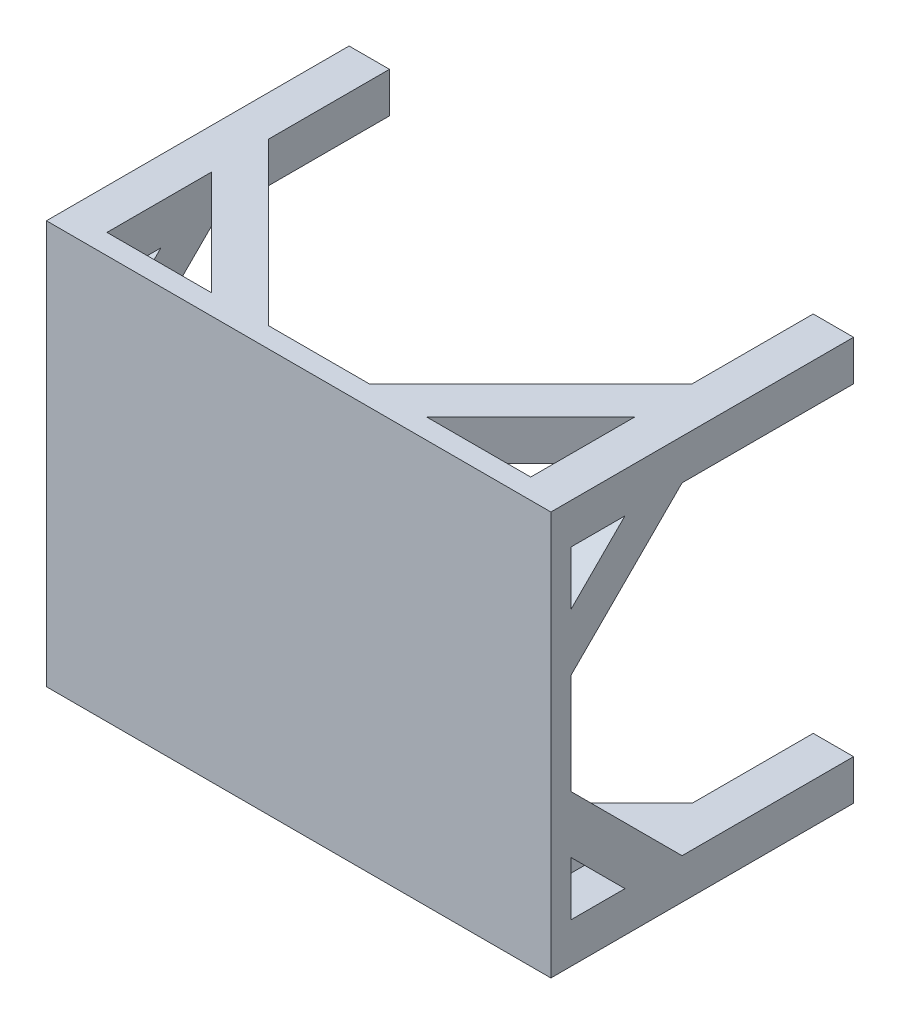
SolidWorks part; units mm, degrees
material "6061 合金"
ref_plane "前视基准面" through (0, 0, 0) normal (0, 0, 1) x (1, 0, 0)
ref_plane "上视基准面" through (0, 0, 0) normal (0, 1, 0) x (1, 0, 0)
ref_plane "右视基准面" through (0, 0, 0) normal (1, 0, 0) x (0, 0, -1)
sketch "草图1" plane through (0, 0, 0) normal (0, 0, 1) x (1, 0, 0)
  line L1 (-250, -200) -> (250, -200)
  line L2 (-250, -200) -> (-250, 200)
  line L3 (-250, 200) -> (250, 200)
  line L4 (250, -200) -> (250, 200)
  line L5 (-250, -200) -> (250, 200) construction
  line L6 (-250, 200) -> (250, -200) construction
  point P0 (0, 0)
  dimension "D1" = 500
  dimension "D2" = 400
extrude "凸台-拉伸1" add sketch "草图1" along normal blind 20
sketch "草图2" plane through (0, 0, 0) normal (0, 0, -1) x (-1, 0, 0)
  line L0 (0, 200) -> (0, 0) construction
  line L1 (-210, 160) -> (-250, 160)
  line L2 (-210, 160) -> (-210, 200)
  line L3 (-210, 200) -> (-250, 200)
  line L4 (-250, 160) -> (-250, 200)
  line L5 (-210, 160) -> (-250, 200) construction
  line L6 (-210, 200) -> (-250, 160) construction
  line L7 (-250, 200) -> (250, 200) construction
  line L8 (0, 0) -> (250, 0) construction
  line L9 (250, 200) -> (250, -200) construction
  line L10 (210, 200) -> (250, 200)
  line L11 (250, 160) -> (250, 200)
  line L12 (210, 160) -> (250, 160)
  line L13 (210, 160) -> (210, 200)
  line L14 (210, -160) -> (210, -200)
  line L15 (210, -160) -> (250, -160)
  line L16 (250, -160) -> (250, -200)
  line L17 (210, -200) -> (250, -200)
  line L18 (-210, -200) -> (-250, -200)
  line L19 (-250, -160) -> (-250, -200)
  line L20 (-210, -160) -> (-250, -160)
  line L21 (-210, -160) -> (-210, -200)
  point P0 (-230, 180)
  dimension "D1" = 40
extrude "凸台-拉伸2" add sketch "草图2" along normal blind 280
sketch "草图3" plane through (0, 200, 0) normal (0, 1, 0) x (1, 0, 0)
  line L0 (-210, 160) -> (-50, 0)
  line L1 (-210, 280) -> (-210, 0) construction
  line L2 (210, 0) -> (-210, 0) construction
  line L3 (-50, 0) -> (-106.5685, 0)
  line L4 (-106.5685, 0) -> (-210, 103.4315)
  line L5 (-210, 103.4315) -> (-210, 160)
  line L6 (0, 0) -> (0, 335.8277) construction
  line L7 (106.5685, 0) -> (210, 103.4315)
  line L8 (50, 0) -> (106.5685, 0)
  line L9 (210, 160) -> (50, 0)
  line L10 (210, 103.4315) -> (210, 160)
  dimension "D1" = 45
  dimension "D2" = 40
  dimension "D3" = 100
extrude "凸台-拉伸3" add sketch "草图3" against normal up to surface (40 mm away) up to face at (230, 160, -140)
extrude "凸台-拉伸4" add sketch "草图3<3>" against normal up to surface (400 mm away) from surface up to face at (0, -200, -135) starting at face at (-230, -160, -140)
sketch "草图3<3>" plane through (0, 200, 0) normal (0, 1, 0) x (1, 0, 0) same geometry as "草图3"
sketch "草图4" plane through (250, 0, 0) normal (1, 0, 0) x (0, 0, -1)
  line L0 (0, 50) -> (110, 160)
  line L1 (0, -160) -> (0, 160) construction
  line L2 (280, 160) -> (0, 160) construction
  line L3 (110, 160) -> (53.4315, 160)
  line L4 (53.4315, 160) -> (0, 106.5685)
  line L5 (0, 106.5685) -> (0, 50)
  line L6 (0, 0) -> (397.7013, 0) construction
  line L7 (53.4315, -160) -> (0, -106.5685)
  line L8 (110, -160) -> (53.4315, -160)
  line L9 (0, -50) -> (110, -160)
  line L10 (0, -106.5685) -> (0, -50)
  dimension "D1" = 45
  dimension "D2" = 100
  dimension "D3" = 40
extrude "凸台-拉伸5" add sketch "草图4" against normal up to surface (40 mm away) up to face at (210, 180, -220)
extrude "凸台-拉伸6" add sketch "草图4<2>" against normal up to surface (500 mm away) from surface up to face at (-250, 0, -135) starting at face at (-210, 180, -220)
sketch "草图4<2>" plane through (250, 0, 0) normal (1, 0, 0) x (0, 0, -1) same geometry as "草图4"
